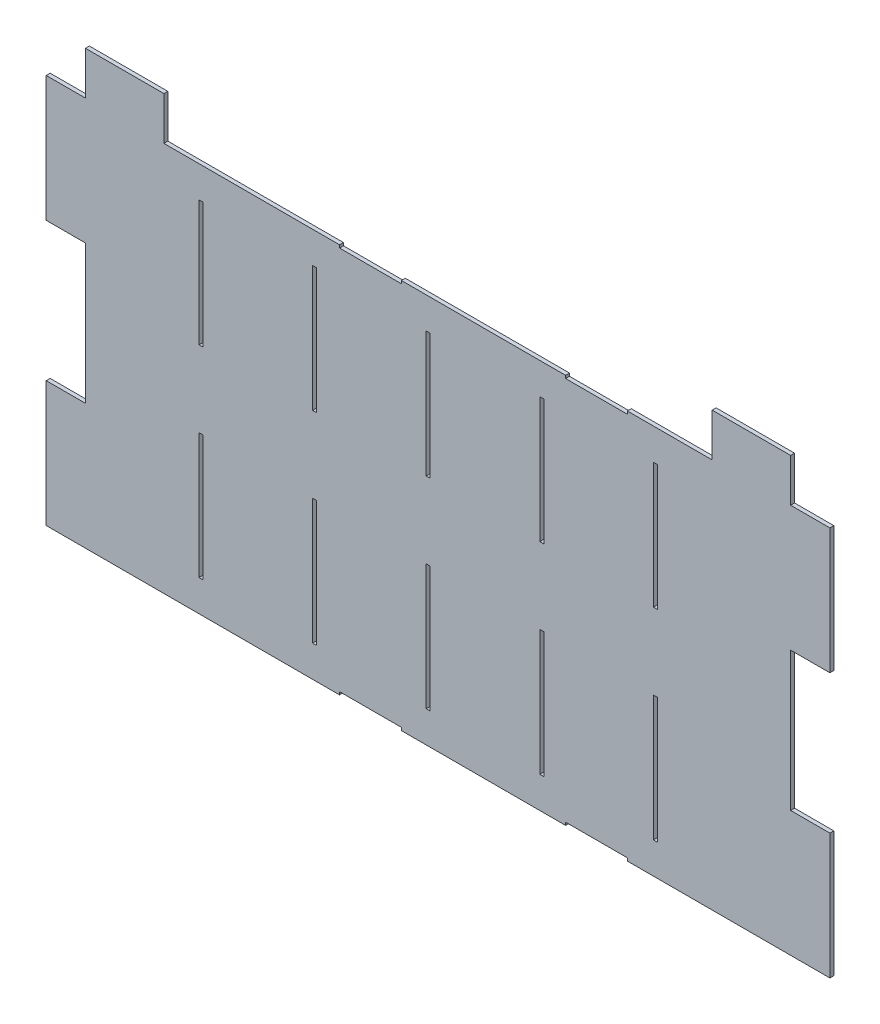
SolidWorks part; units mm, degrees
material "Custom Plastic"
ref_plane "X-Y Datum" through (0, 0, 0) normal (0, 0, 1) x (1, 0, 0)
ref_plane "X-Z Datum" through (0, 0, 0) normal (0, 1, 0) x (1, 0, 0)
ref_plane "Y-Z Datum" through (0, 0, 0) normal (1, 0, 0) x (0, 0, -1)
sketch "Sketch1" plane through (0, 0, 0) normal (0, 0, 1) x (1, 0, 0)
  line L0 (-285.4305, 0) -> (285.4305, 0) construction
  line L1 (-285.4305, -157.7875) -> (285.4305, -157.7875)
  line L2 (-285.4305, -157.7875) -> (-285.4305, 157.7875)
  line L3 (-285.4305, 157.7875) -> (285.4305, 157.7875)
  line L4 (285.4305, -157.7875) -> (285.4305, 157.7875)
  line L5 (-285.4305, -157.7875) -> (285.4305, 157.7875) construction
  line L6 (-285.4305, 157.7875) -> (285.4305, -157.7875) construction
  line L7 (-282.2555, -154.615) -> (-282.2555, 154.615)
  line L8 (-280.6655, -153.025) -> (-195.0655, -153.025)
  line L9 (-280.6655, -153.025) -> (-280.6655, 153.025)
  line L10 (-280.6655, 153.025) -> (-195.0655, 153.025)
  line L11 (-195.0655, -153.025) -> (-195.0655, 153.025)
  line L12 (-280.6655, -153.025) -> (-195.0655, 153.025) construction
  line L13 (-280.6655, 153.025) -> (-195.0655, -153.025) construction
  line L14 (-282.2555, 154.615) -> (-193.4755, 154.615)
  line L15 (-193.4755, -154.615) -> (-193.4755, 154.615)
  line L16 (-282.2555, -154.615) -> (-193.4755, -154.615)
  line L17 (-190.3005, 154.615) -> (-101.5205, 154.615)
  line L18 (-188.7105, 153.025) -> (-103.1105, 153.025)
  line L19 (-190.3005, -154.615) -> (-190.3005, 154.615)
  line L20 (-188.7105, -153.025) -> (-188.7105, 153.025)
  line L21 (-101.5205, -154.615) -> (-101.5205, 154.615)
  line L22 (-103.1105, -153.025) -> (-103.1105, 153.025)
  line L23 (-188.7105, -153.025) -> (-103.1105, -153.025)
  line L24 (-190.3005, -154.615) -> (-101.5205, -154.615)
  line L25 (-188.7105, -153.025) -> (-103.1105, 153.025) construction
  line L26 (-188.7105, 153.025) -> (-103.1105, -153.025) construction
  line L27 (-98.3455, 154.615) -> (-9.5655, 154.615)
  line L28 (-96.7555, 153.025) -> (-11.1555, 153.025)
  line L29 (-98.3455, -154.615) -> (-98.3455, 154.615)
  line L30 (-96.7555, -153.025) -> (-96.7555, 153.025)
  line L31 (-9.5655, -154.615) -> (-9.5655, 154.615)
  line L32 (-11.1555, -153.025) -> (-11.1555, 153.025)
  line L33 (-96.7555, -153.025) -> (-11.1555, -153.025)
  line L34 (-98.3455, -154.615) -> (-9.5655, -154.615)
  line L35 (-96.7555, -153.025) -> (-11.1555, 153.025) construction
  line L36 (-96.7555, 153.025) -> (-11.1555, -153.025) construction
  line L37 (-6.3905, 154.615) -> (82.3895, 154.615)
  line L38 (-4.8005, 153.025) -> (80.7995, 153.025)
  line L39 (-6.3905, -154.615) -> (-6.3905, 154.615)
  line L40 (-4.8005, -153.025) -> (-4.8005, 153.025)
  line L41 (82.3895, -154.615) -> (82.3895, 154.615)
  line L42 (80.7995, -153.025) -> (80.7995, 153.025)
  line L43 (-4.8005, -153.025) -> (80.7995, -153.025)
  line L44 (-6.3905, -154.615) -> (82.3895, -154.615)
  line L45 (-4.8005, -153.025) -> (80.7995, 153.025) construction
  line L46 (-4.8005, 153.025) -> (80.7995, -153.025) construction
  line L47 (85.5645, 154.615) -> (174.3445, 154.615)
  line L48 (87.1545, 153.025) -> (172.7545, 153.025)
  line L49 (85.5645, -154.615) -> (85.5645, 154.615)
  line L50 (87.1545, -153.025) -> (87.1545, 153.025)
  line L51 (174.3445, -154.615) -> (174.3445, 154.615)
  line L52 (172.7545, -153.025) -> (172.7545, 153.025)
  line L53 (87.1545, -153.025) -> (172.7545, -153.025)
  line L54 (85.5645, -154.615) -> (174.3445, -154.615)
  line L55 (87.1545, -153.025) -> (172.7545, 153.025) construction
  line L56 (87.1545, 153.025) -> (172.7545, -153.025) construction
  point P0 (0, 0)
  point P8 (-237.8655, 0)
  dimension "D1" = 570.861
  dimension "D2" = 315.575
  dimension "D3" = 306.05
  dimension "D4" = 85.6
  dimension "D5" = 3.175
  dimension "D8" = 3.175
  dimension "D6" = 1.59
  dimension "D7" = 5
extrude "Boss-Extrude1" add sketch "Sketch1" along normal blind 3.175 contours L8 L11 L10 L9 | L20 L23 L22 L18 | L30 L33 L32 L28 | L50 L53 L52 L48 | L49 L54 L51 L47 L53 L50 L48 L52 | L1 L4 L3 L2 L54 L49 L47 L51 L44 L39 L37 L41 L34 L29 L27 L31 L24 L19 L17 L21 L16 L7 L14 L15 | L40 L43 L42 L38 | L7 L16 L15 L14 L11 L8 L9 L10 | L19 L24 L21 L17 L23 L20 L18 L22 | L29 L34 L31 L27 L33 L30 L28 L32 | L39 L44 L41 L37 L43 L40 L38 L42 region at (-284.7782, 0, 0) region at (-281.9338, 0, 0) region at (-237.8655, 0, 0) region at (-145.9105, 154.2933, 0) region at (-145.9105, 0, 0) region at (-53.9555, 154.2933, 0) region at (-53.9555, 0, 0) region at (37.9995, 154.2933, 0) region at (37.9995, 0, 0) region at (129.9545, 154.2933, 0) region at (129.9545, 0, 0)
sketch "Sketch2" plane through (0, 0, 3.175) normal (0, 0, 1) x (1, 0, 0)
  line L0 (-190.3005, -154.615) -> (-193.4755, -154.615) construction
  line L1 (-191.888, -154.615) -> (-191.888, 157.7875) construction
  line L2 (-285.4305, 157.7875) -> (285.4305, 157.7875) construction
  line L4 (-193.4755, -30.7875) -> (-190.3005, -30.7875)
  line L5 (-193.4755, -30.7875) -> (-193.4755, -132.3875)
  line L6 (-193.4755, -132.3875) -> (-190.3005, -132.3875)
  line L7 (-190.3005, -30.7875) -> (-190.3005, -132.3875)
  line L8 (-193.4755, -30.7875) -> (-190.3005, -132.3875) construction
  line L9 (-193.4755, -132.3875) -> (-190.3005, -30.7875) construction
  line L12 (-285.4305, -157.7875) -> (285.4305, -157.7875) construction
  point P8 (-191.888, -81.5875)
  dimension "D1" = 76.2
  dimension "D2" = 3.175
  dimension "D3" = 101.6
extrude "Cut-Extrude1" cut sketch "Sketch2" against normal blind 3.175
sketch "Sketch7" plane through (0, 0, 3.175) normal (0, 0, 1) x (1, 0, 0)
  line L1 (103.2695, -155.5015) -> (153.2695, -155.5015)
  line L2 (103.2695, -155.5015) -> (103.2695, -157.7875)
  line L3 (103.2695, -157.7875) -> (153.2695, -157.7875)
  line L4 (153.2695, -155.5015) -> (153.2695, -157.7875)
  line L5 (-79.7305, -155.5015) -> (-29.7305, -155.5015)
  line L6 (-79.7305, -155.5015) -> (-79.7305, -157.7875)
  line L7 (-79.7305, -157.7875) -> (-29.7305, -157.7875)
  line L8 (-29.7305, -155.5015) -> (-29.7305, -157.7875)
extrude "Cut-Extrude5" cut sketch "Sketch7" against normal blind 3.175
mirror "Mirror3" about plane through (0, 0, 0) normal (0, 1, 0) of "Cut-Extrude1"
pattern_linear "LPattern2" count 5 spacing 91.96 along (1, 0, 0) of "Mirror3"
sketch "Sketch9" plane through (0, 0, 0) normal (0, 0, -1) x (-1, 0, 0)
  line L0 (-301.3055, -56.1875) -> (-301.3055, -157.7875) construction
  line L9 (-285.4305, 157.7875) -> (-221.9305, 157.7875)
  line L10 (-285.4305, 157.7875) -> (-285.4305, 192.7125)
  line L11 (-285.4305, 192.7125) -> (-221.9305, 192.7125)
  line L12 (-221.9305, 157.7875) -> (-221.9305, 192.7125)
  line L13 (-285.4305, 157.7875) -> (-317.1805, 157.7875)
  line L14 (-285.4305, 157.7875) -> (-285.4305, 56.1875)
  line L15 (-285.4305, 56.1875) -> (-317.1805, 56.1875)
  line L16 (-317.1805, 157.7875) -> (-317.1805, 56.1875)
  line L17 (-317.1805, 106.9875) -> (-285.4305, 106.9875) construction
  line L18 (-301.3055, 157.7875) -> (-301.3055, 113.3375)
  line L19 (-301.3055, 113.3375) -> (-301.3055, 56.1875) construction
  line L20 (-285.4305, -157.7875) -> (-317.1805, -157.7875)
  line L21 (-285.4305, -157.7875) -> (-285.4305, -88.7618)
  line L25 (-285.4305, -88.7618) -> (-285.4305, -56.1875)
  line L26 (-285.4305, -56.1875) -> (-317.1805, -56.1875)
  line L28 (-317.1805, -56.1875) -> (-317.1805, -157.7875)
  line L29 (-317.1805, -106.9875) -> (-285.4305, -106.9875) construction
  line L30 (-301.3055, -56.1875) -> (-301.3055, -106.9875) construction
  line L31 (-301.3055, -106.9875) -> (-301.3055, -157.7875) construction
  line L32 (-301.3055, -56.1875) -> (-301.3055, -106.9875) construction
  line L33 (-301.3055, -106.9875) -> (-301.3055, -157.7875) construction
  circle A0 centre (-301.3055, 135.5625) radius 3 construction
  circle A1 centre (-301.3055, 84.7625) radius 3 construction
  circle A2 centre (-301.3055, -81.5875) radius 3 construction
  circle A3 centre (-301.3055, -132.3875) radius 3 construction
  dimension "D1" = 6
  dimension "D2" = 6
  dimension "D3" = 63.5
  dimension "D4" = 34.925
  dimension "D5" = 101.6
  dimension "D6" = 31.75
  dimension "D7" = 31.75
  dimension "D8" = 101.6
extrude "Boss-Extrude3" add sketch "Sketch9" against normal blind 3.175 contours L13 L16 L15 L14 | L9 L12 L11 L10 | L26 L28 L20 L21 L25 A3 A2 region at (253.6805, 175.25, 0) region at (301.3055, 106.9875, 0) region at (301.3055, -106.9875, 0)
mirror "Mirror4" about plane through (0, 0, 0) normal (1, 0, 0) of "Boss-Extrude3"
mirror "Mirror5" about plane through (0, 0, 0) normal (0, 1, 0) of "Cut-Extrude5"
